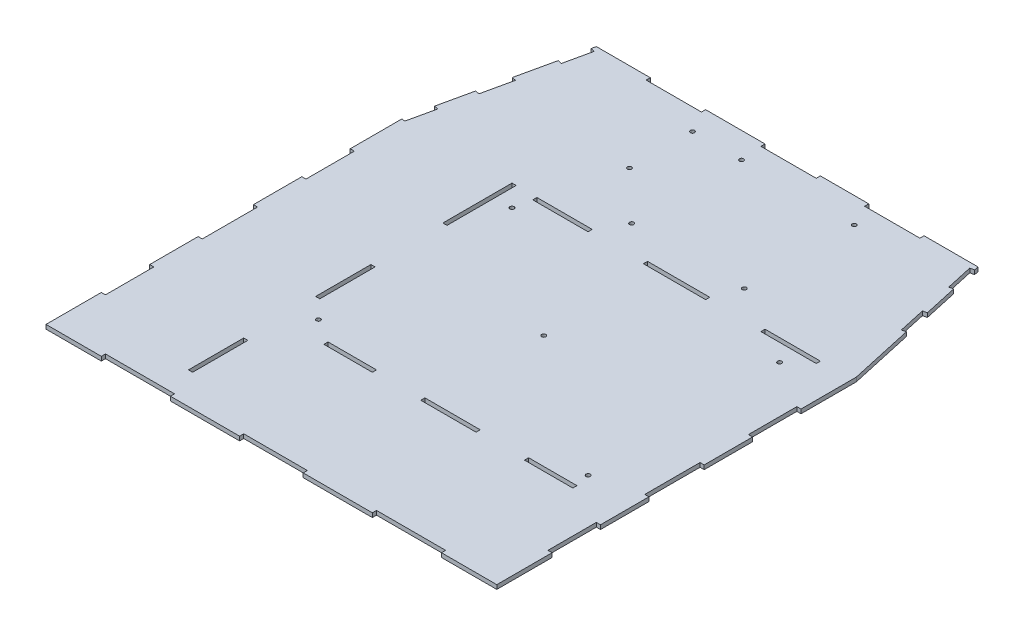
SolidWorks part; units mm, degrees
ref_plane "Front Plane" through (0, 0, 0) normal (0, 0, 1) x (1, 0, 0)
ref_plane "Top Plane" through (0, 0, 0) normal (0, 1, 0) x (1, 0, 0)
ref_plane "Right Plane" through (0, 0, 0) normal (1, 0, 0) x (0, 0, -1)
sketch "Sketch1" plane through (0, 0, 0) normal (0, 1, 0) x (1, 0, 0)
  line L0 (-138, 185) -> (-163, 72)
  line L1 (-163, 185) -> (163, 185)
  line L2 (-163, 185) -> (-163, -188)
  line L3 (-163, -188) -> (163, -188)
  line L4 (163, 185) -> (163, -188)
  line L5 (138, 185) -> (163, 72)
  dimension "D1" = 373
  dimension "D2" = 326
  dimension "D3" = 163
  dimension "D4" = 185
  dimension "D5" = 25
  dimension "D6" = 113
  dimension "D7" = 25
  dimension "D8" = 113
extrude "Boss-Extrude1" add sketch "Sketch1" along normal blind 3 contours L5 L1 L0 L2 L3 L4 region at (0, 0, 5.04)
sketch "Sketch2" plane through (0, 0, 0) normal (0, -1, 0) x (1, 0, 0)
  line L0 (-163, 188) -> (163, 188) construction
  line L1 (123, 188) -> (73, 188)
  line L2 (123, 188) -> (123, 185)
  line L3 (123, 185) -> (73, 185)
  line L4 (73, 188) -> (73, 185)
  line L5 (163, -72) -> (163, 188) construction
  line L6 (23, 188) -> (-23, 188)
  line L7 (23, 188) -> (23, 185)
  line L8 (23, 185) -> (-23, 185)
  line L9 (-23, 188) -> (-23, 185)
  line L10 (-73, 188) -> (-123, 188)
  line L11 (-73, 188) -> (-73, 185)
  line L12 (-73, 185) -> (-123, 185)
  line L13 (-123, 188) -> (-123, 185)
  line L18 (-163, -72) -> (-163, 188) construction
  dimension "D1" = 40
  dimension "D2" = 50
  dimension "D3" = 3
  dimension "D4" = 3
  dimension "D5" = 50
  dimension "D6" = 46
  dimension "D7" = 40
  dimension "D8" = 50
  dimension "D9" = 3
extrude "Cut-Extrude1" cut sketch "Sketch2" against normal blind 4
sketch "Sketch4" plane through (-163, 0, 0) normal (-1, 0, 0) x (0, 0, 1)
  line L0 (-72, 0) -> (188, 0) construction
  line L1 (148, 0) -> (113, 0)
  line L2 (148, 0) -> (148, 3)
  line L3 (148, 3) -> (113, 3)
  line L4 (113, 0) -> (113, 3)
  line L5 (-72, 3) -> (188, 3) construction
  line L6 (188, 3) -> (188, 0) construction
  line L7 (-32, 3) -> (3, 3)
  line L8 (-32, 3) -> (-32, 0)
  line L9 (-32, 0) -> (3, 0)
  line L10 (3, 3) -> (3, 0)
  line L11 (38, 3) -> (78, 3)
  line L12 (38, 3) -> (38, 0)
  line L13 (38, 0) -> (78, 0)
  line L14 (78, 3) -> (78, 0)
  line L15 (-72, 3) -> (-72, 0) construction
  dimension "D1" = 35
  dimension "D2" = 40
  dimension "D3" = 40
  dimension "D4" = 35
  dimension "D5" = 40
  dimension "D6" = 35
extrude "Cut-Extrude2" cut sketch "Sketch4" against normal blind 3
extrude "Cut-Extrude3" cut sketch "Sketch4<2>" along normal blind 3 from surface starting at face at (163, 1.5, 58)
sketch "Sketch4<2>" plane through (-163, 0, 0) normal (-1, 0, 0) x (0, 0, 1) same geometry as "Sketch4"
sketch "Sketch5" plane through (0, 0, -185) normal (0, 0, -1) x (-1, 0, 0)
  line L0 (-139, 3) -> (-99, 3) construction
  line L1 (99, 3) -> (59, 3)
  line L2 (99, 3) -> (99, 0)
  line L3 (99, 0) -> (59, 0)
  line L4 (59, 3) -> (59, 0)
  line L5 (138, 0) -> (-138, 0) construction
  line L6 (-139, 103) -> (-139, 3) construction
  line L7 (16, 3) -> (-24, 3)
  line L8 (16, 3) -> (16, 0)
  line L9 (16, 0) -> (-24, 0)
  line L10 (-24, 3) -> (-24, 0)
  line L11 (-99, 3) -> (-59, 3)
  line L12 (-99, 3) -> (-99, 0)
  line L13 (-99, 0) -> (-59, 0)
  line L14 (-59, 3) -> (-59, 0)
  line L15 (139, 3) -> (139, 103) construction
  dimension "D1" = 40
  dimension "D2" = 40
  dimension "D3" = 40
  dimension "D4" = 40
  dimension "D5" = 35
  dimension "D6" = 40
extrude "Cut-Extrude4" cut sketch "Sketch5" against normal blind 3
sketch "Sketch6" plane through (0, 0, 0) normal (0, -1, 0) x (1, 0, 0)
  line L1 (-80, 165) -> (-83, 165)
  line L2 (-80, 165) -> (-80, 125)
  line L3 (-80, 125) -> (-83, 125)
  line L4 (-83, 165) -> (-83, 125)
  line L5 (-80, 73) -> (-83, 73)
  line L6 (-80, 73) -> (-80, 33)
  line L7 (-80, 33) -> (-83, 33)
  line L8 (-83, 73) -> (-83, 33)
  line L9 (-80, -19) -> (-83, -19)
  line L10 (-80, -19) -> (-80, -69)
  line L11 (-80, -69) -> (-83, -69)
  line L12 (-83, -19) -> (-83, -69)
extrude "Cut-Extrude5" cut sketch "Sketch6" against normal through all both and the other way through all
sketch "Sketch7" plane through (0, 0, 0) normal (0, -1, 0) x (1, 0, 0)
  line L1 (140, -69) -> (100, -69)
  line L2 (140, -69) -> (140, -66)
  line L3 (140, -66) -> (100, -66)
  line L4 (100, -69) -> (100, -66)
  line L5 (60, -69) -> (15, -69)
  line L6 (60, -69) -> (60, -66)
  line L7 (60, -66) -> (15, -66)
  line L8 (15, -69) -> (15, -66)
  line L9 (-25, -69) -> (-65, -69)
  line L10 (-25, -69) -> (-25, -66)
  line L11 (-25, -66) -> (-65, -66)
  line L12 (-65, -69) -> (-65, -66)
extrude "Cut-Extrude6" cut sketch "Sketch7" against normal through all both and the other way through all
sketch "Sketch8" plane through (0, 0, 0) normal (0, -1, 0) x (-1, 0, 0)
  line L0 (135.7494, 181.2848) -> (138.6786, 181.9329)
  line L1 (138.6786, 181.9329) -> (142.9989, 162.4051)
  line L2 (142.9989, 162.4051) -> (140.0697, 161.757)
  line L3 (140.0697, 161.757) -> (135.7494, 181.2848)
  line L4 (146.0836, 134.5743) -> (149.0127, 135.2224)
  line L5 (149.0127, 135.2224) -> (153.7996, 113.5856)
  line L6 (153.7996, 113.5856) -> (150.8705, 112.9375)
  line L7 (150.8705, 112.9375) -> (146.0836, 134.5743)
  line L8 (156.2709, 88.5278) -> (160.5912, 69)
  line L9 (160.5912, 69) -> (163.5203, 69.648)
  line L10 (163.5203, 69.648) -> (159.2, 89.1758)
  line L11 (159.2, 89.1758) -> (156.2709, 88.5278)
extrude "Cut-Extrude7" cut sketch "Sketch8" against normal through all both and the other way through all
sketch "Sketch9" plane through (0, 0, 0) normal (0, -1, 0) x (1, 0, 0)
  line L0 (138.6786, -181.9329) -> (135.7494, -181.2848)
  line L1 (135.7494, -181.2848) -> (140.0697, -161.757)
  line L2 (140.0697, -161.757) -> (145.4701, -137.3473) construction
  line L3 (135.7494, -181.2848) -> (140.0697, -161.757) construction
  line L4 (140.0697, -161.757) -> (142.9989, -162.4051)
  line L5 (142.9989, -162.4051) -> (138.6786, -181.9329)
  line L6 (145.4701, -137.3473) -> (148.3993, -137.9953)
  line L7 (148.3993, -137.9953) -> (152.7196, -118.4675)
  line L8 (152.7196, -118.4675) -> (149.7904, -117.8195)
  line L9 (149.7904, -117.8195) -> (145.4701, -137.3473)
extrude "Cut-Extrude8" cut sketch "Sketch9" against normal through all both and the other way through all
sketch "Sketch10" plane through (0, 0, 0) normal (0, -1, 0) x (1, 0, 0)
  line L1 (130, 97) -> (95, 97)
  line L2 (130, 97) -> (130, 100)
  line L3 (130, 100) -> (95, 100)
  line L4 (95, 97) -> (95, 100)
  line L5 (60, 97) -> (20, 97)
  line L6 (60, 97) -> (60, 100)
  line L7 (60, 100) -> (20, 100)
  line L8 (20, 97) -> (20, 100)
  line L9 (-15, 97) -> (-50, 97)
  line L10 (-15, 97) -> (-15, 100)
  line L11 (-15, 100) -> (-50, 100)
  line L12 (-50, 97) -> (-50, 100)
extrude "Cut-Extrude9" cut sketch "Sketch10" against normal through all both and the other way through all
sketch "Sketch11" plane through (0, 0, 0) normal (0, -1, 0) x (1, 0, 0)
  line L0 (99, -185) -> (138, -185) construction
  circle A0 centre (67, -166.5) radius 1.5
  circle A1 centre (-14.5, -166.5) radius 1.5
  circle A2 centre (-50, -166.5) radius 1.5
  circle A3 centre (67, -87) radius 1.5
  circle A4 centre (-14.5, -87) radius 1.5
  circle A6 centre (-50, -120.9) radius 1.5
  dimension "D1" = 3
  dimension "D2" = 18.5
  dimension "D4" = 3
  dimension "D5" = 81.5
  dimension "D6" = 3
  dimension "D7" = 35.5
  dimension "D8" = 3
  dimension "D9" = 79.5
  dimension "D10" = 3
  dimension "D11" = 81.5
  dimension "D14" = 45.6
  dimension "D15" = 35.5
  dimension "D16" = 3
  dimension "D3" = 72
extrude "Cut-Extrude10" cut sketch "Sketch11" against normal through all both and the other way through all
sketch "Sketch12" plane through (0, 0, 0) normal (0, -1, 0) x (1, 0, 0)
  line L2 (-25, -66) -> (-65, -66) construction
  line L3 (-80, -69) -> (-80, -19) construction
  line L4 (-25, -66) -> (-65, -66) construction
  line L5 (-80, -69) -> (-80, -19) construction
  circle A0 centre (126, -53.5) radius 1.5
  circle A2 centre (127.5, 86.492) radius 1.5
  circle A3 centre (-67.5, -53.5) radius 1.5
  circle A6 centre (-67.5, 86.5) radius 1.5
  circle A10 centre (24, 15) radius 1.5
  point P11 (0, 0)
  point P15 (0, 0)
  point P17 (0, 0)
  dimension "D1" = 3
  dimension "D2" = 25
  dimension "D3" = 25
  dimension "D4" = 140
  dimension "D5" = 140
  dimension "D6" = 3
  dimension "D7" = 3
  dimension "D8" = 3
  dimension "D9" = 195
  dimension "D14" = 3
  dimension "D15" = 195
extrude "Cut-Extrude11" cut sketch "Sketch12" against normal through all both and the other way through all
